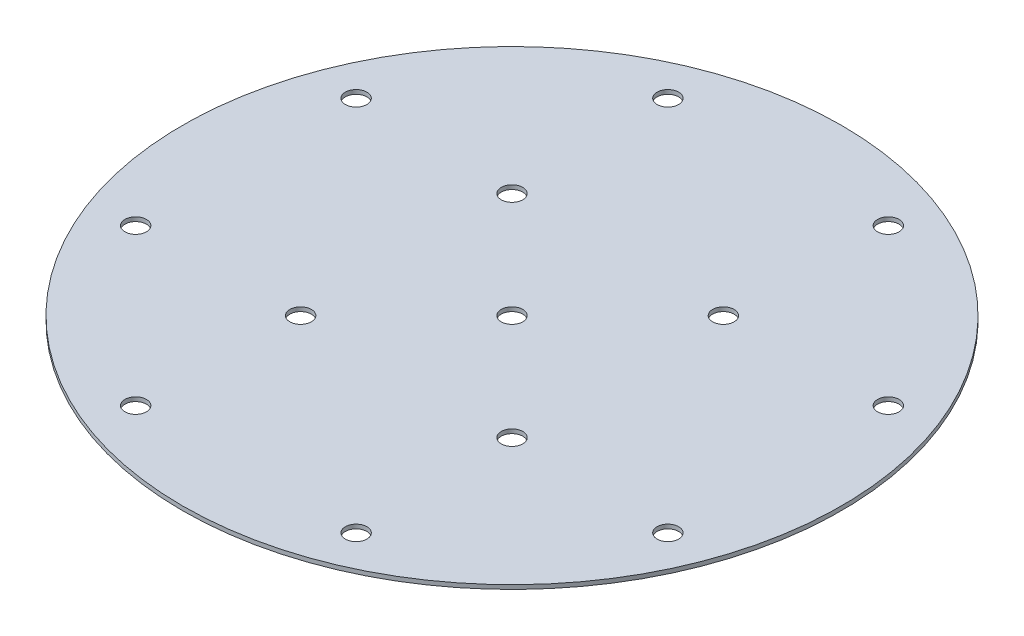
SolidWorks part; units mm, degrees
material "6061-T6 (SS)"
ref_plane "Front Plane" through (0, 0, 0) normal (0, 0, 1) x (1, 0, 0)
ref_plane "Top Plane" through (0, 0, 0) normal (0, 1, 0) x (1, 0, 0)
ref_plane "Right Plane" through (0, 0, 0) normal (1, 0, 0) x (0, 0, -1)
sketch "Sketch2" plane through (0, 0, 0) normal (1, 0, 0) x (0, 0, -1)
  line L0 (0, 0) -> (-79.375, 0)
  line L1 (-79.375, 0) -> (-79.375, 1)
  line L2 (-79.375, 1) -> (0, 1)
  line L5 (0, 1) -> (0, 0)
  dimension "D1" = 79.375
  dimension "D2" = 1
ref_axis "Axis1" through (0, -0.05, 0) along (0, 1, 0)
revolve "Revolve1" add sketch "Sketch2" angle 360 about axis through (0, -0.05, 0) along (0, 1, 0)
hole_wizard "#6 (0.204) Diameter Hole1" positions "Sketch6" profile "Sketch7" hole size "#6" standard "ANSI Inch" end condition through all
sketch "Sketch6" plane through (0, 1, 0) normal (0, 1, 0) x (1, 0, 0)
  line L0 (0, 0) -> (-53.438, 129.0108) construction
  line L2 (0, 0) -> (0, 109.0908) construction
  line L3 (0, 0) -> (-73.3329, 30.3755) construction
  line L4 (0, 0) -> (-47.7784, 47.7784) construction
  circle A0 centre (0, 0) radius 79.375 construction
  point P0 (-26.5487, 64.0941)
  point P11 (264.7437, 73.7878)
  point P20 (-64.0941, 26.5487)
  point P22 (-25.4558, 25.4558)
  dimension "D1" = 22.5
  dimension "D2" = 69.375
  dimension "D3" = 69.375
  dimension "D4" = 45
  dimension "D6" = 22.5
  dimension "D5" = 36
sketch "Sketch7" plane through (-26.5487, 1, -64.0941) normal (1, 0, 0) x (0, 0, 1)
  line L0 (0, 0) -> (0, 1)
  line L1 (0, 1) -> (2.5908, 1)
  line L2 (2.5908, 1) -> (2.5908, 0)
  line L5 (2.5908, 0) -> (0, 0)
  line L11 (0, -6.35) -> (0, 107.95) construction
  dimension "Thru Hole Dia." = 5.1816
  dimension "Thru Hole Depth" = 1
pattern_circular "CirPattern3" count 4 over 360 about axis through (0, -0.05, 0) along (0, 1, 0) of "#6 (0.204) Diameter Hole1"
hole_wizard "#6 (0.204) Diameter Hole2" positions "Sketch8" profile "Sketch9" hole size "#6" standard "ANSI Inch" end condition through all
sketch "Sketch8" plane through (0, 1, 0) normal (0, 1, 0) x (1, 0, 0)
  line L0 (0, 0) -> (106.3094, -1.7118) construction
  point P7 (0, 0)
sketch "Sketch9" plane through (0, 1, 0) normal (1, 0, 0) x (0, 0, 1)
  line L0 (0, 0) -> (0, 1)
  line L1 (0, 1) -> (2.5908, 1)
  line L2 (2.5908, 1) -> (2.5908, 0)
  line L5 (2.5908, 0) -> (0, 0)
  line L11 (0, -6.35) -> (0, 107.95) construction
  dimension "Thru Hole Dia." = 5.1816
  dimension "Thru Hole Depth" = 1
equation "\"TubeDiameter\" = 6.250in"
equation "\"D1@Sketch2\"=\"TubeDiameter\"/2"
equation "\"D2@Sketch6\"=\"TubeDiameter\"/2-10mm"
equation "\"D3@Sketch6\"=\"TubeDiameter\"/2-10mm"
